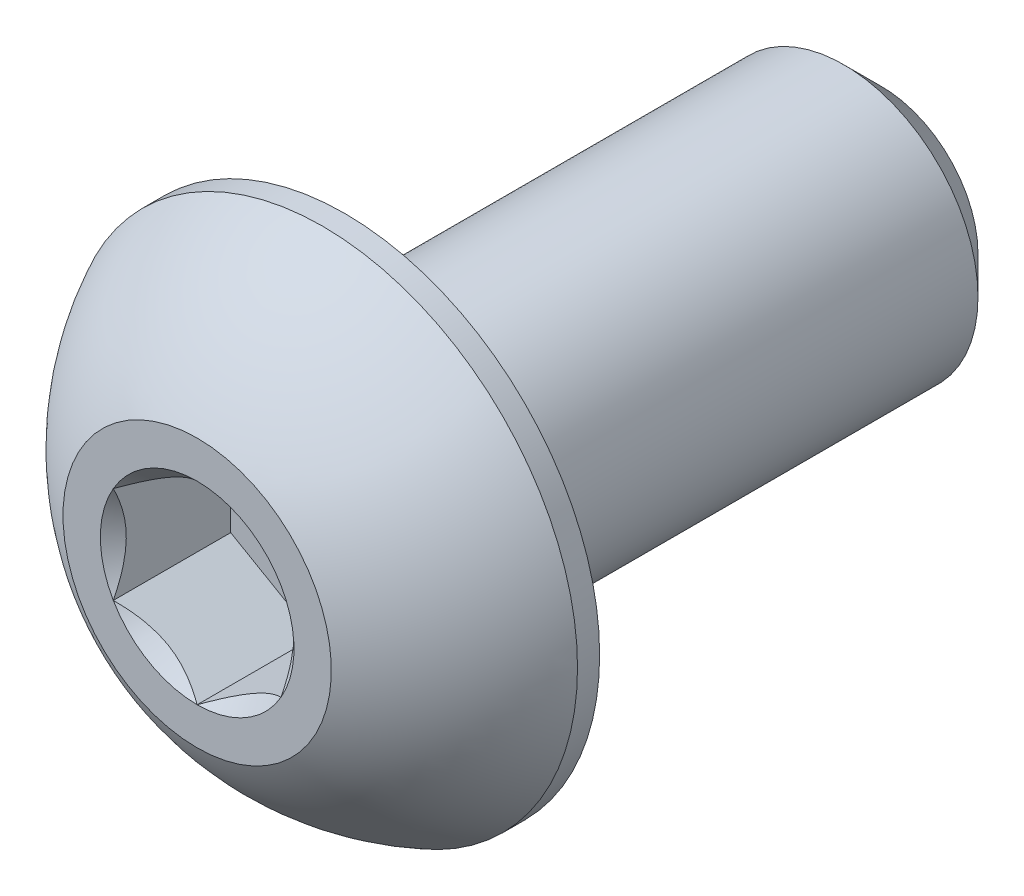
SolidWorks part; units mm, degrees
material "Alloy Steel"
ref_plane "Front Plane" through (0, 0, 0) normal (0, 0, 1) x (1, 0, 0)
ref_plane "Top Plane" through (0, 0, 0) normal (0, 1, 0) x (1, 0, 0)
ref_plane "Right Plane" through (0, 0, 0) normal (1, 0, 0) x (0, 0, -1)
sketch "Sketch1" plane through (0, 0, 0) normal (1, 0, 0) x (0, 0, -1)
  line L0 (-5.1, 0) -> (5.1, 0) construction
  line L1 (-2.9, 3.8) -> (-2.9, -3.8) construction
  line L2 (5.1, 2) -> (5.1, -2) construction
  line L3 (5.0563, 2.0758) -> (5.4063, 1.4696) construction
  line L4 (5.4063, 1.4696) -> (5.7563, 2.0758) construction
  line L5 (5.7563, 2.0758) -> (5.0563, 2.0758) construction
  line L6 (5.1, 2) -> (5.7125, 2) construction
  line L7 (5.4063, 2.0758) -> (5.4063, 2) construction
  line L8 (5.4063, 2) -> (5.4063, 1.5453) construction
  line L9 (5.4063, 1.5453) -> (5.4063, 1.4696) construction
  line L10 (5.3625, 1.5453) -> (5.45, 1.5453)
  line L11 (5.0781, 2.0379) -> (5.7344, 2.0379)
  line L12 (5.45, 1.5453) -> (5.7344, 2.0379)
  line L13 (5.3625, 1.5453) -> (5.0781, 2.0379)
  line L14 (-5.1, 1.25) -> (-5.1, -1.25) construction
  line L15 (5.1, 2) -> (-2.9, 2) construction
  point P3 (-2.9, 0)
  point P6 (-3.35, 0)
  point P21 (5.4063, 2.0379)
  point P24 (-3.23, 3.8)
  point P25 (3.35, -2)
  point P26 (-5.1, 2)
  dimension "Head Height" = 2.2
  dimension "Length" = 8
  dimension "Head Dia" = 7.6
  dimension "Thread Dia" = 4
  dimension "Pitch" = 0.7
  dimension "D2" = 0.0875
  dimension "Drive Size" = 2.5
  dimension "D1" = 1.75
  dimension "D3" = 0.33
  dimension "D4" = 1.75
sketch "Sketch2" plane through (0, 0, 0) normal (1, 0, 0) x (0, 0, -1)
  line L0 (-5.1, 0) -> (5.1, 0)
  line L1 (5.1, 0) -> (5.1, 1.44)
  line L2 (5.1, 2) -> (5.1, -2) construction
  line L3 (5.1, 1.44) -> (4.54, 2)
  line L4 (4.54, 2) -> (-2.9, 2)
  line L5 (-2.9, 3.8) -> (-2.9, -3.8) construction
  line L6 (-2.9, 2) -> (-2.9, 3.8)
  line L7 (-2.9, 3.8) -> (-3.23, 3.8)
  line L8 (5.1, 2) -> (5.7125, 2) construction
  line L9 (-5.1, 0) -> (-5.1, 2)
  arc A0 (-5.1, 2) -> (-3.23, 3.8) centre (-1.3736, 0) cw
  dimension "D1" = 0.56
  dimension "D2" = 45
revolve "Revolve1" add sketch "Sketch2" angle 360 about L0
sketch "Sketch3" plane through (0, 0, 5.1) normal (0, 0, 1) x (1, 0, 0)
  line L1 (0, 1.4434) -> (-1.25, 0.7217)
  line L2 (-1.25, 0.7217) -> (-1.25, -0.7217)
  line L3 (-1.25, -0.7217) -> (0, -1.4434)
  line L4 (0, -1.4434) -> (1.25, -0.7217)
  line L5 (1.25, -0.7217) -> (1.25, 0.7217)
  line L6 (1.25, 0.7217) -> (0, 1.4434)
  circle A0 centre (0, 0) radius 1.25 construction
  dimension "D1" = 2.5
extrude "Cut-Extrude1" cut sketch "Sketch3" against normal up to vertex (1.75 mm away) up to point (0, 0, 3.35)
sketch "Sketch4" plane through (0, 0, 5.1) normal (0, 0, 1) x (1, 0, 0)
  circle A0 centre (0, 0) radius 1.4434
extrude "Cut-Extrude2" cut sketch "Sketch4" against normal blind 10 draft 45
split "Split1" [suppressed] bodies to split 106
sketch "Sketch5" [suppressed] plane through (0, 0, -5.1) normal (0, 0, -1) x (-1, 0, 0)
  circle A0 centre (0, 0) radius 2 construction
  circle A1 centre (0, 0) radius 2
curve "Helix/Spiral1" [suppressed] pitch 0.7 height 8.7 turns 12.4286
sketch "Sketch6" [suppressed] plane through (0, 0, 0) normal (1, 0, 0) x (0, 0, -1)
  line L0 (5.3625, 1.5453) -> (5.45, 1.5453) construction
  line L1 (5.3625, 1.5453) -> (5.0781, 2.0379) construction
  line L2 (5.0781, 2.0379) -> (5.7344, 2.0379) construction
  line L3 (5.45, 1.5453) -> (5.7344, 2.0379) construction
  line L4 (5.3625, 1.5453) -> (5.45, 1.5453)
  line L5 (5.3625, 1.5453) -> (5.0781, 2.0379)
  line L6 (5.0781, 2.0379) -> (5.7344, 2.0379)
  line L7 (5.45, 1.5453) -> (5.7344, 2.0379)
sweep "Cut-Sweep1" [suppressed] cut profiles "Sketch6" path "Helix/Spiral1"
sketch "Sketch7" [suppressed] plane through (0, 0, 2.9) normal (0, 0, -1) x (-1, 0, 0)
  circle A1 centre (0, 0) radius 2
  circle A2 centre (0, 0) radius 2
  dimension "D1" = 0
extrude "Boss-Extrude1" [suppressed] add sketch "Sketch7" along normal blind 10 draft 30
equation "\"D2@Sketch1\" = \"Pitch@Sketch1\" / 8"
equation "\"D1@Sketch1\"=\"Drive Size@Sketch1\"*.7"
equation "\"D3@Sketch1\"=\"Head Height@Sketch1\"*.15"
equation "\"D1@Sketch2\"=\"Pitch@Sketch1\"*.8"
equation "\"D1@Sketch3\"=\"Drive Size@Sketch1\""
equation "\"D4@Helix/Spiral1\"=\"Pitch@Sketch1\""
equation "\"D3@Helix/Spiral1\"=\"Length@Sketch1\"+\"Pitch@Sketch1\""
equation "\"D4@Sketch1\"=\"Pitch@Sketch1\"*2.5"
